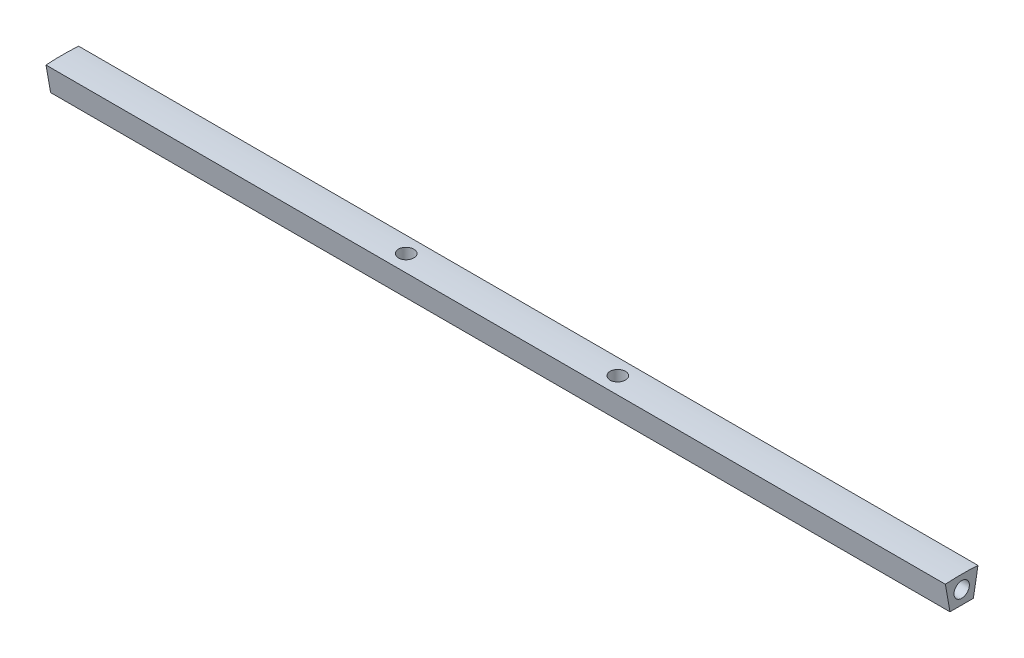
SolidWorks part; units mm, degrees
ref_plane "Спереди" through (0, 0, 0) normal (0, 0, 1) x (1, 0, 0)
ref_plane "Сверху" through (0, 0, 0) normal (0, 1, 0) x (1, 0, 0)
ref_plane "Справа" through (0, 0, 0) normal (1, 0, 0) x (0, 0, -1)
sketch "Эскиз1" plane through (0, 0, 0) normal (1, 0, 0) x (0, 0, -1)
  line L0 (-3.0855, 17.4987) -> (-2.2117, 12.5434)
  line L1 (0, -1000) -> (0, 49000) construction
  line L2 (2.2117, 12.5434) -> (3.0855, 17.4987)
  line L3 (-2.2117, 12.5434) -> (2.2117, 12.5434)
  arc A0 (-35.7, 0) -> (35.7, 0) centre (0, -27.3954) cw construction
  arc A1 (-29.146, 0) -> (29.146, 0) centre (0, -27.3954) cw construction
  arc A2 (-3.0855, 17.4987) -> (3.0855, 17.4987) centre (0, -27.3954) cw
  dimension "D1" = 45
  dimension "D2" = 5
  dimension "D3" = 71.4
  dimension "D4" = 10
extrude "Бобышка-Вытянуть1" add sketch "Эскиз1" along normal mid plane 170
sketch "Эскиз2" plane through (85, 0, 0) normal (1, 0, 0) x (0, 0, -1)
  circle A0 centre (0, 15.1046) radius 1.45
  arc A1 (3.0855, 17.4987) -> (-3.0855, 17.4987) centre (0, -27.3954) ccw construction
  arc A2 (3.0855, 17.4987) -> (-3.0855, 17.4987) centre (0, -27.3954) ccw construction
  circle A3 centre (0, -27.3954) radius 42.5 construction
  dimension "D1" = 85
  dimension "D2" = 2.9
extrude "Вырез-Вытянуть1" cut sketch "Эскиз2" against normal blind 10
mirror "Зеркальное отражение1" about plane through (0, 0, 0) normal (1, 0, 0) of "Вырез-Вытянуть1"
sketch "Эскиз3" plane through (0, 12.5434, 0) normal (0, -1, 0) x (1, 0, 0)
  line L0 (0, -1000) -> (0, 49000) construction
  line L1 (-1000, 0) -> (49000, 0) construction
  circle A0 centre (-20, 0) radius 1.45
  circle A1 centre (20, 0) radius 1.45
  dimension "D2" = 2.9
  dimension "D1" = 20
extrude "Вырез-Вытянуть2" cut sketch "Эскиз3" against normal blind 10
